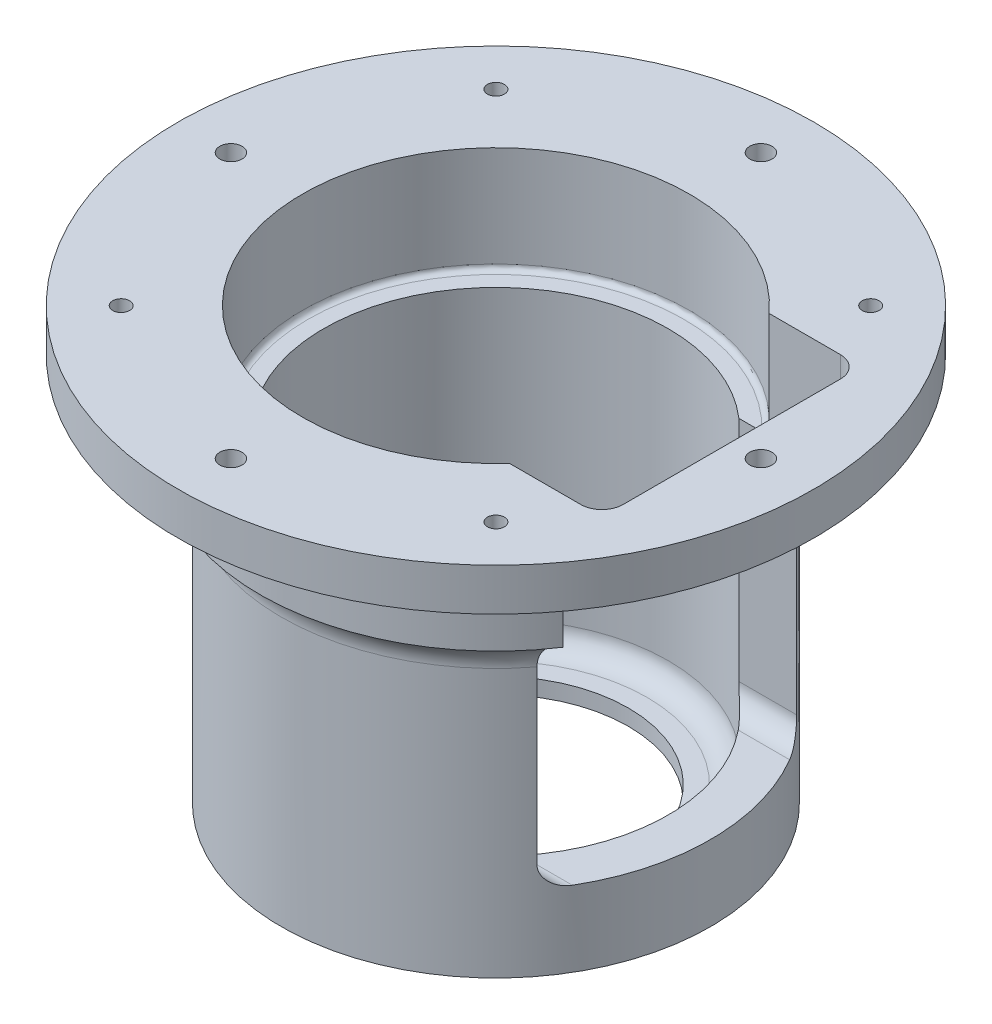
SolidWorks part; units mm, degrees
ref_plane "Front Plane" through (0, 0, 0) normal (0, 0, 1) x (1, 0, 0)
ref_plane "Top Plane" through (0, 0, 0) normal (0, 1, 0) x (1, 0, 0)
ref_plane "Right Plane" through (0, 0, 0) normal (1, 0, 0) x (0, 0, -1)
sketch "Sketch3" plane through (0, 0, 0) normal (0, 0, 1) x (1, 0, 0)
  line L0 (32.5, 12) -> (27.5, 3) construction
  line L1 (0, 0) -> (40.5, 0)
  line L2 (0, 0) -> (0, 3)
  line L3 (0, 3) -> (40.5, 3)
  line L4 (40.5, 0) -> (40.5, 3)
  line L5 (40.5, 3) -> (32.5, 3)
  line L6 (40.5, 3) -> (40.5, 81.25)
  line L7 (40.5, 81.25) -> (32.5, 81.25)
  line L8 (32.5, 3) -> (32.5, 81.25)
  line L10 (40.5, 81.25) -> (60, 81.25)
  line L11 (40.5, 81.25) -> (40.5, 73.25)
  line L12 (40.5, 73.25) -> (60, 73.25)
  line L13 (60, 81.25) -> (60, 73.25)
  line L14 (32.5, 81.25) -> (44.5, 81.25)
  line L15 (32.5, 81.25) -> (32.5, 56.25)
  line L16 (32.5, 56.25) -> (44.5, 56.25)
  line L17 (44.5, 81.25) -> (44.5, 56.25)
  line L18 (32.5, 81.25) -> (36.5, 81.25)
  line L19 (32.5, 81.25) -> (32.5, 61.25)
  line L20 (32.5, 61.25) -> (36.5, 61.25)
  line L21 (36.5, 81.25) -> (36.5, 61.25)
  dimension "D1" = 3
  dimension "D2" = 8
  dimension "D3" = 32.5
  dimension "D4" = 78.25
  dimension "D5" = 9
  dimension "D6" = 27.5
  dimension "D7" = 8
  dimension "D8" = 60
  dimension "D9" = 25
  dimension "D10" = 5
  dimension "D11" = 8
  dimension "D12" = 4
revolve "Revolve1" add sketch "Sketch3" angle 360 about L2 region at (20.25, 1.5, 0) region at (36.5, 29.625, 0) region at (37.8333, 67.0833, 0) region at (42.5, 64.75, 0) region at (42.5, 77.25, 0) region at (52.25, 77.25, 0)
sketch "Sketch5" plane through (0, 0, 0) normal (0, -1, 0) x (1, 0, 0)
  circle A0 centre (0, 0) radius 25
  dimension "D1" = 50
extrude "Cut-Extrude2" cut sketch "Sketch5" against normal through all
sketch "Sketch4" plane through (0, 81.25, 0) normal (0, 1, 0) x (1, 0, 0)
  line L1 (0, -24.5) -> (44.5, -24.5)
  line L2 (0, -24.5) -> (0, 24.5)
  line L3 (0, 24.5) -> (44.5, 24.5)
  line L4 (44.5, -24.5) -> (44.5, 24.5)
  circle A1 centre (0, 0) radius 44.5 construction
  circle A2 centre (0, 0) radius 44.5 construction
  point P4 (0, 0)
  dimension "D1" = 49
extrude "Cut-Extrude1" cut sketch "Sketch4" against normal blind 67
sketch "Sketch6" plane through (0, 81.25, 0) normal (0, 1, 0) x (1, 0, 0)
  line L0 (0, 0) -> (35.3553, 35.3553) construction
  line L1 (35.3553, 35.3553) -> (35.3553, 0) construction
  line L2 (35.3553, 0) -> (0, 0) construction
  line L3 (-35.3553, 35.3553) -> (35.3553, 35.3553) construction
  circle A0 centre (0, 0) radius 50 construction
  circle A1 centre (35.3553, 35.3553) radius 1.6
  circle A2 centre (50, 0) radius 2.1
  circle A3 centre (35.3553, -35.3553) radius 1.6
  circle A4 centre (-35.3553, -35.3553) radius 1.6
  circle A5 centre (-35.3553, 35.3553) radius 1.6
  circle A6 centre (0, 50) radius 2.1
  circle A7 centre (0, -50) radius 2.1
  circle A8 centre (-50, 0) radius 2.1
  point P18 (0, 0)
  point P24 (0, 0)
  dimension "D1" = 100
  dimension "D2" = 3.2
  dimension "D4" = 4.2
  dimension "D3" = 4
  dimension "D5" = 4
extrude "Cut-Extrude3" cut sketch "Sketch6" against normal through all
fillet "Fillet2" radius 4 1 edges at (0, 3, -32.5)
fillet "Fillet4" radius 4 4 edges at (26.8016, 14.25, -24.5) (26.8016, 14.25, 24.5) (44.5, 77.25, -24.5) (44.5, 77.25, 24.5)
fillet "Fillet7" radius 6 1 edges at (-40.5, 56.25, 0)
fillet "Fillet8" radius 3 1 edges at (-44.5, 73.25, 0)
fillet "Fillet9" radius 1 1 edges at (-36.5, 61.25, 0)
